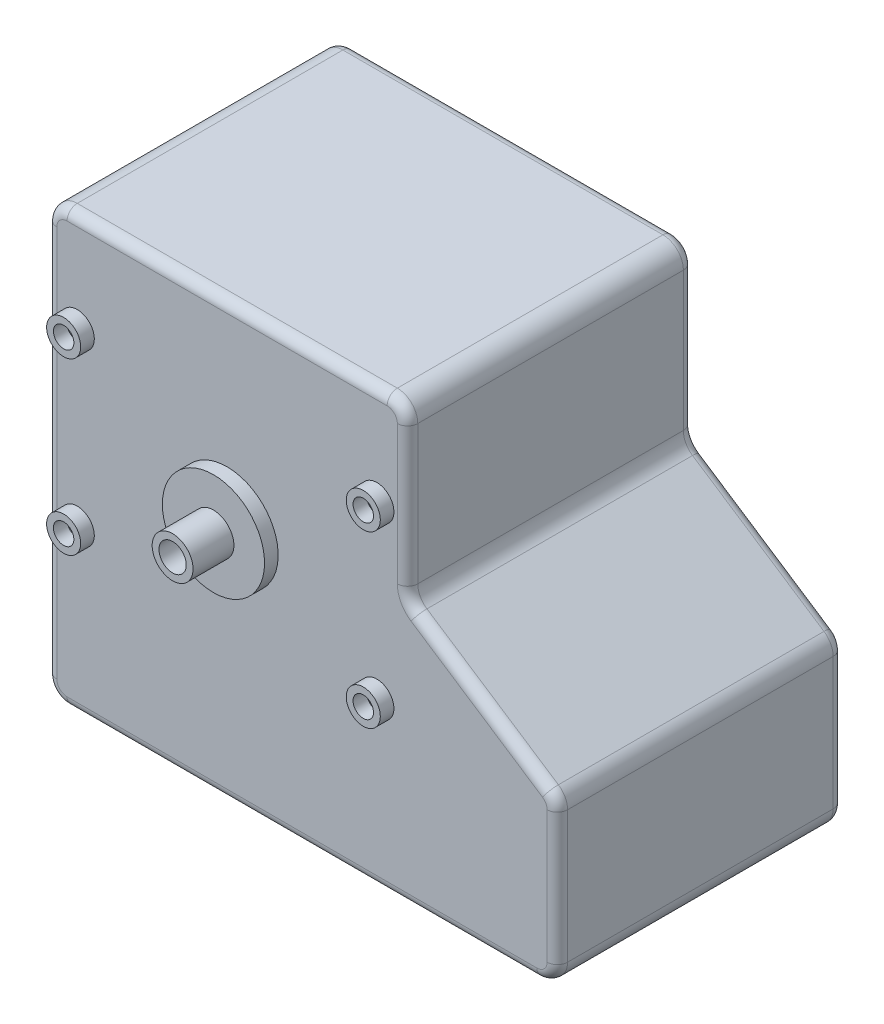
SolidWorks part; units mm, degrees
ref_plane "Front Plane" through (0, 0, 0) normal (0, 0, 1) x (1, 0, 0)
ref_plane "Top Plane" through (0, 0, 0) normal (0, 1, 0) x (1, 0, 0)
ref_plane "Right Plane" through (0, 0, 0) normal (1, 0, 0) x (0, 0, -1)
sketch "Sketch2" plane through (0, 0, 0) normal (0, 0, 1) x (1, 0, 0)
  line L0 (26.5, 6.75) -> (48.5, -7.75)
  line L1 (-26.5, -31.75) -> (26.5, -31.75)
  line L2 (-26.5, -31.75) -> (-26.5, 31.75)
  line L3 (-26.5, 31.75) -> (26.5, 31.75)
  line L4 (26.5, 6.75) -> (26.5, 31.75)
  line L5 (-26.5, -31.75) -> (26.5, 31.75) construction
  line L6 (-26.5, 31.75) -> (26.5, -31.75) construction
  line L7 (48.5, -7.75) -> (48.5, -31.75)
  line L8 (48.5, -31.75) -> (26.5, -31.75)
  line L9 (55, 0) -> (-55, 0) construction
  point P0 (0, 0)
  dimension "D1" = 63.5
  dimension "D2" = 53
  dimension "D3" = 75
  dimension "D4" = 24
  dimension "D5" = 31.75
  dimension "D6" = 25
extrude "Boss-Extrude1" add sketch "Sketch2" along normal mid plane 42
sketch "Sketch3" plane through (0, 0, 21) normal (0, 0, 1) x (1, 0, 0)
  line L0 (0, -55) -> (0, 55) construction
  line L1 (-22, -7.75) -> (22, -7.75) construction
  line L2 (-22, -7.75) -> (-22, 17.25) construction
  line L3 (-22, 17.25) -> (22, 17.25) construction
  line L4 (22, -7.75) -> (22, 17.25) construction
  line L5 (-22, -7.75) -> (22, 17.25) construction
  line L6 (-22, 17.25) -> (22, -7.75) construction
  line L7 (-26.5, -31.75) -> (48.5, -31.75) construction
  circle A0 centre (-22, 17.25) radius 1.5
  circle A1 centre (-22, -7.75) radius 1.5
  circle A2 centre (22, -7.75) radius 1.5
  circle A3 centre (22, 17.25) radius 1.5
  circle A4 centre (-22, 17.25) radius 2.5
  circle A5 centre (22, 17.25) radius 2.5
  circle A6 centre (-22, -7.75) radius 2.5
  circle A7 centre (22, -7.75) radius 2.5
  point P0 (0, 4.75)
  dimension "D4" = 3
  dimension "D5" = 5
  dimension "D1" = 36.5
  dimension "D2" = 44
  dimension "D3" = 25
extrude "Boss-Extrude2" add sketch "Sketch3" along normal blind 2
sketch "Sketch5" plane through (0, 0, 21) normal (0, 0, 1) x (1, 0, 0)
  line L0 (0, -55) -> (0, 55) construction
  line L1 (-26.5, -31.75) -> (48.5, -31.75) construction
  circle A0 centre (0, 3.25) radius 7.5
  dimension "D1" = 15
  dimension "D2" = 35
extrude "Boss-Extrude4" add sketch "Sketch5" along normal blind 2
fillet "Fillet1" radius 3 6 edges at (-26.5, -31.75, 0) (-26.5, 31.75, 0) (48.5, -31.75, 0) (48.5, -7.75, 0) (26.5, 6.75, 0) (26.5, 31.75, 0)
fillet "Fillet2" radius 1.5 24 edges at (26.8587, 6.9432, -21) (37.5, -0.5, -21) (48.1413, -7.9432, -21) (48.5, -19.0579, -21) (47.6213, -30.8713, -21) (11, -31.75, -21) (-25.6213, -30.8713, -21) (-26.5, 0, -21) (-25.6213, 30.8713, -21) (0, 31.75, -21) (25.6213, 30.8713, -21) (25.6213, 30.8713, 21) (26.5, 18.5579, 21) (26.8587, 6.9432, 21) (37.5, -0.5, 21) (48.1413, -7.9432, 21) (48.5, -19.0579, 21) (47.6213, -30.8713, 21) (11, -31.75, 21) (-25.6213, -30.8713, 21) (-26.5, 0, 21) (-25.6213, 30.8713, 21) (26.5, 18.5579, -21) (0, 31.75, 21)
sketch "Sketch7" plane through (0, 0, 23) normal (0, 0, 1) x (1, 0, 0)
  circle A0 centre (0, 3.25) radius 3
  dimension "D1" = 6
extrude "Boss-Extrude6" add sketch "Sketch7" along normal blind 6
sketch "Sketch8" plane through (0, 0, 29) normal (0, 0, 1) x (1, 0, 0)
  circle A0 centre (0, 3.25) radius 2
  dimension "D1" = 4
extrude "Cut-Extrude2" cut sketch "Sketch8" against normal through all
sketch "Sketch9" plane through (0, 0, -21) normal (0, 0, -1) x (-1, 0, 0)
  line L1 (-7.5, -9.25) -> (7.5, -9.25)
  line L2 (-12.5, -4.25) -> (-12.5, 10.75)
  line L3 (-7.5, 15.75) -> (7.5, 15.75)
  line L4 (12.5, -4.25) -> (12.5, 10.75)
  line L5 (-12.5, -9.25) -> (12.5, 15.75) construction
  line L6 (-12.5, 15.75) -> (12.5, -9.25) construction
  arc A0 (7.5, -9.25) -> (12.5, -4.25) centre (7.5, -4.25) ccw
  arc A1 (-7.5, -9.25) -> (-12.5, -4.25) centre (-7.5, -4.25) cw
  arc A2 (-12.5, 10.75) -> (-7.5, 15.75) centre (-7.5, 10.75) cw
  arc A3 (7.5, 15.75) -> (12.5, 10.75) centre (7.5, 10.75) cw
  point P0 (0, 3.25)
  dimension "D3" = 5
  dimension "D1" = 25
  dimension "D2" = 25
extrude "Boss-Extrude7" add sketch "Sketch9" along normal blind 8
